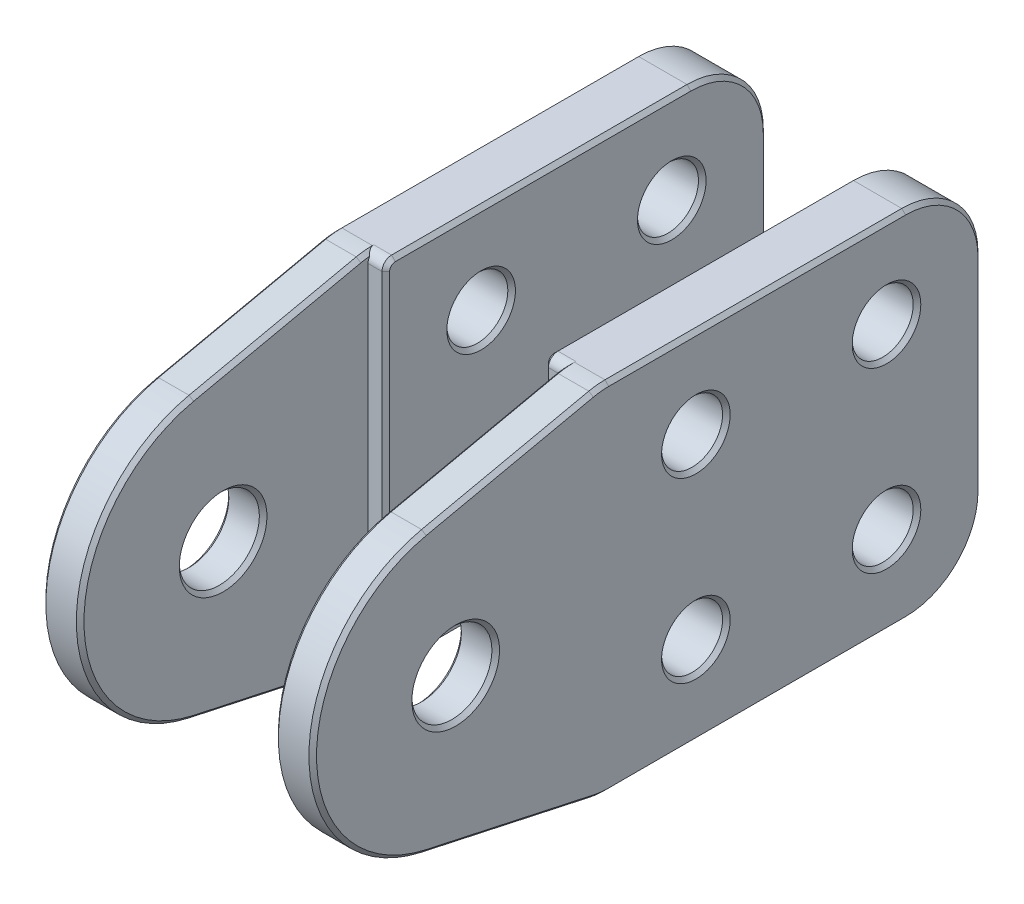
SolidWorks part; units mm, degrees
ref_plane "Front Plane" through (0, 0, 0) normal (1, 0, 0) x (0, 1, 0)
ref_plane "Top Plane" through (0, 0, 0) normal (0, 0, 1) x (0, 1, 0)
ref_plane "Right Plane" through (0, 0, 0) normal (0, 1, 0) x (-1, 0, 0)
sketch "Sketch1" plane through (0, 0, 0) normal (1, 0, 0) x (0, 1, 0)
  line L0 (0, 0) -> (0, 15.2)
  line L1 (0, 0) -> (-18.645, 0)
  line L2 (0, 0) -> (0, -40)
  line L3 (0, -40) -> (-18.645, -40)
  line L4 (-18.645, 0) -> (-18.645, -40)
  line L5 (0, 15.2) -> (0, 30.2)
  line L6 (-18.645, 0) -> (-14.6592, 18.3791)
  line L7 (-9.3225, 0) -> (-9.3225, -40) construction
  circle A0 centre (0, 15.2) radius 15
  circle A1 centre (0, 15.2) radius 4.2
  circle A2 centre (-9.3225, -10) radius 3.2
  circle A3 centre (-9.3225, -30) radius 3.2
  arc A4 (-18.645, -1) -> (-17.645, 0) centre (-17.645, -1) cw
  dimension "D1" = 30
  dimension "D2" = 8.4
  dimension "D5" = 6.4
  dimension "D9" = 1
  dimension "D3" = 15.2
  dimension "D4" = 40
  dimension "D6" = 10
  dimension "D7" = 10
  dimension "D8" = 18.645
ref_plane "Plane1" through (10.2, 0, 0) normal (1, 0, 0) x (0, 1, 0)
ref_plane "Plane2" through (8.33, 0, 0) normal (1, 0, 0) x (0, 1, 0)
extrude "Boss-Extrude1" add sketch "Sketch1" along normal blind 4 from surface contours A1 L5 A0 L0 | A0 L6 L1 L0 | L4 A4 L1 region at (0, -13.2067, 4.2056) region at (0, -6.7561, 15.2) region at (0, -18.4216, -0.2234) starting at plane "Plane1"
extrude "Boss-Extrude2" add sketch "Sketch1<3>" along normal up to surface (14.2 mm away) from surface contours L7 L1 L4 L3 A3 A2 | L1 L7 A2 A3 L3 L2 region at (0, -4.3494, -20) region at (0, -14.293, -20.0125) up to face at (14.2, -9.5109, 10.0967) starting at plane "Plane2"
sketch "Sketch1<3>" plane through (0, 0, 0) normal (1, 0, 0) x (0, 1, 0) same geometry as "Sketch1"
fillet "Fillet1" radius 8 1 edges at (12.2, -18.645, 0)
fillet "Fillet2" radius 8 1 edges at (11.265, -18.645, -40)
chamfer "Chamfer1" distance 0.4 angle 45 21 edges at (14.2, -9.3225, -33.2) (8.33, -9.3225, -33.2) (14.2, -9.3225, -13.2) (8.33, -9.3225, -13.2) (14.2, -18.645, -16.4287) (14.2, -9.4158, 26.8766) (14.2, -18.5994, -0.0049) (14.2, -16.5613, 9.6085) (14.2, -4.2, 15.2) (10.2, -4.2, 15.2) (10.2, -18.645, -0.9287) (10.2, -9.4158, 26.8766) (10.2, -18.5994, -0.0049) (10.2, -16.5613, 9.6085) (8.33, -18.645, -16.5) (8.33, -18.3521, -0.2929) (8.33, -8.8225, 0) (14.2, -5.3225, -40) (14.2, -16.3019, -37.6569) (8.33, -5.3225, -40) (8.33, -16.3019, -37.6569)
mirror "Mirror1" about plane through (14.2, 0, -291566.29) normal (0, 1, 0) of bodies 102
mirror "Mirror3" about plane through (0, 0, 0) normal (1, 0, 0) of bodies 103
equation "\"D3@Sketch1\"=\"D1@Sketch1\"/2+0.2"
equation "\"D6@Sketch1\"=\"D4@Sketch1\"/4"
equation "\"D7@Sketch1\"=\"D6@Sketch1\""
